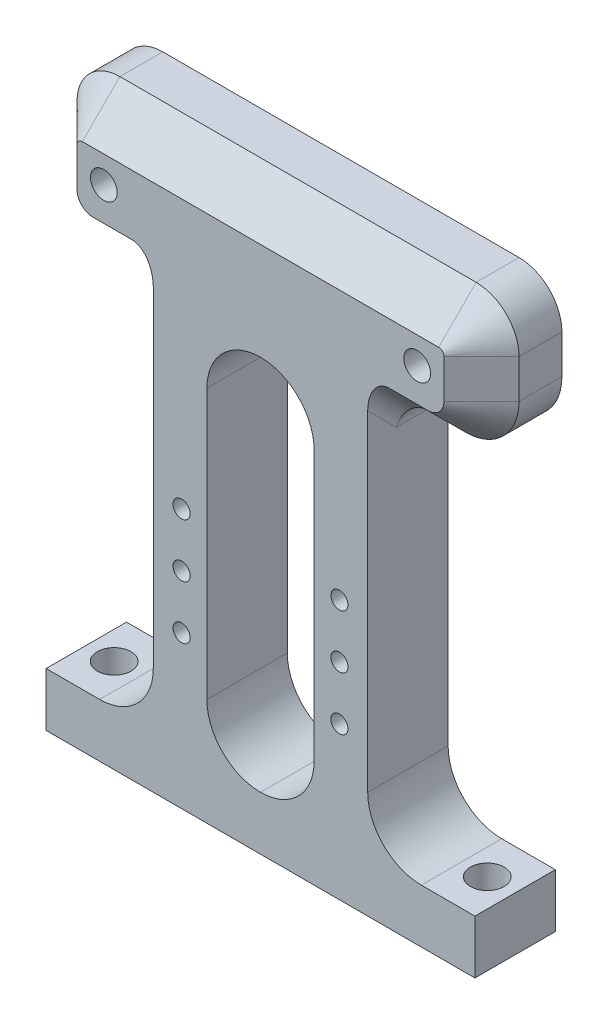
SolidWorks part; units mm, degrees
ref_plane "Front Plane" through (0, 0, 0) normal (0, 0, 1) x (1, 0, 0)
ref_plane "Top Plane" through (0, 0, 0) normal (0, 1, 0) x (1, 0, 0)
ref_plane "Right Plane" through (0, 0, 0) normal (1, 0, 0) x (0, 0, -1)
sketch "Sketch1" plane through (0, 0, 0) normal (0, 0, 1) x (1, 0, 0)
  line L0 (26.181, 50.9851) -> (26.1811, 61.92)
  line L1 (-25.4, 0) -> (25.4, 0)
  line L2 (21.1011, 67) -> (-21.1011, 67)
  line L3 (-26.1811, 61.92) -> (-26.181, 50.9851)
  line L4 (0, 0) -> (0, 101.7984) construction
  line L5 (-59.2795, 0) -> (59.2795, 0) construction
  line L6 (18.5611, 59.38) -> (59.2795, 0) construction
  line L7 (-18.5611, 59.38) -> (-59.2795, 0) construction
  line L8 (12.7, 6.35) -> (12.7, 50.9851)
  line L9 (12.7, 50.9851) -> (26.181, 50.9851)
  line L10 (-12.7, 50.9851) -> (-26.181, 50.9851)
  line L11 (-12.7, 6.35) -> (-12.7, 50.9851)
  line L13 (-25.4, 0) -> (-25.4, 6.35)
  line L14 (-25.4, 6.35) -> (-12.7, 6.35)
  line L16 (25.4, 0) -> (25.4, 6.35)
  line L17 (25.4, 6.35) -> (12.7, 6.35)
  circle A0 centre (-18.5611, 59.38) radius 1.5875
  circle A1 centre (18.5611, 59.38) radius 1.5875
  arc A4 (26.1811, 61.92) -> (21.1011, 67) centre (21.1011, 61.92) ccw
  arc A5 (-21.1011, 67) -> (-26.1811, 61.92) centre (-21.1011, 61.92) ccw
  point P31 (-26.1811, 67)
  dimension "D1" = 3.175
  dimension "D13" = 5.08
  dimension "D2" = 7.62
  dimension "D3" = 50.8
  dimension "D4" = 7.62
  dimension "D5" = 37.1221
  dimension "D6" = 67
  dimension "D7" = 71.9999
  dimension "D8" = 16.0149
  dimension "D9" = 25.4
  dimension "D10" = 6.35
extrude "Extrude1" add sketch "Sketch1" against normal blind 9.525
sketch "Sketch2" plane through (0, 0, -9.525) normal (0, 0, -1) x (-1, 0, 0)
  line L0 (-12.7, 6.35) -> (-12.7, 50.9851) construction
  line L1 (-6.35, 50.9851) -> (6.35, 50.9851)
  line L2 (-6.35, 50.9851) -> (-6.35, 6.35)
  line L3 (-6.35, 6.35) -> (6.35, 6.35)
  line L4 (6.35, 50.9851) -> (6.35, 6.35)
  line L5 (-12.7, 50.9851) -> (-26.181, 50.9851) construction
  line L6 (-25.4, 6.35) -> (-12.7, 6.35) construction
  dimension "D1" = 12.7
  dimension "D2" = 6.35
extrude "Cut-Extrude1" cut sketch "Sketch2" against normal through all
fillet "Fillet1" radius 6.35 2 edges at (-26.181, 50.9851, -4.7625) (26.181, 50.9851, -4.7625)
chamfer "Chamfer1" distance 4.445 angle 45 9 edges at (-16.2655, 50.9851, 0) (-24.3212, 52.845, 0) (-26.1811, 59.6275, 0) (-24.6932, 65.5121, 0) (16.2655, 50.9851, 0) (0, 67, 0) (24.3212, 52.845, 0) (24.6932, 65.5121, 0) (26.1811, 59.6275, 0) tangent propagation no
fillet "Fillet2" radius 6.35 4 edges at (6.35, 50.9851, -4.7625) (-6.35, 50.9851, -4.7625) (6.35, 6.35, -4.7625) (-6.35, 6.35, -4.7625)
fillet "Fillet3" radius 6.35 2 edges at (-12.7, 6.35, -4.7625) (12.7, 6.35, -4.7625)
sketch "Sketch3" plane through (0, 6.35, 0) normal (0, 1, 0) x (1, 0, 0)
  line L0 (-25.4, 4.7625) -> (-19.4878, 4.7625) construction
  line L1 (-25.4, 9.525) -> (-25.4, 0) construction
  line L2 (-22.098, 9.525) -> (-22.098, 0) construction
  line L6 (-19.05, 9.525) -> (-25.4, 9.525) construction
  line L7 (-19.05, 0) -> (-25.4, 0) construction
  circle A0 centre (-22.098, 4.7625) radius 2
  dimension "D2" = 4
  dimension "D1" = 3.302
extrude "Cut-Extrude2" cut sketch "Sketch3" against normal through all
mirror "Mirror2" about plane through (0, 0, 0) normal (1, 0, 0) of "Cut-Extrude2"
sketch "Sketch4" plane through (0, 0, 0) normal (0, 0, 1) x (1, 0, 0)
  line L1 (25.4, 0) -> (9.3451, 0) construction
  line L2 (25.4, 0) -> (25.4, 30.7426) construction
  line L3 (25.4, 30.7426) -> (9.3451, 30.7426) construction
  line L4 (9.3451, 0) -> (9.3451, 30.7426) construction
  circle A0 centre (9.3451, 30.7426) radius 1.016
  dimension "D1" = 2.032
  dimension "D2" = 16.0549
  dimension "D3" = 30.7426
extrude "Extrude2" cut sketch "Sketch4" against normal through all
mirror "Mirror3" about plane through (0, 0, 0) normal (1, 0, 0) of "Extrude2"
pattern_linear "LPattern1" count 3 spacing 6.35 along (0, -1, 0) of "Mirror3", "Extrude2"
fillet "Fillet5" radius 2.54 4 edges at (-12.7, 50.9851, -6.985) (-12.7, 53.2076, -2.2225) (12.7, 53.2076, -2.2225) (12.7, 50.9851, -6.985)
